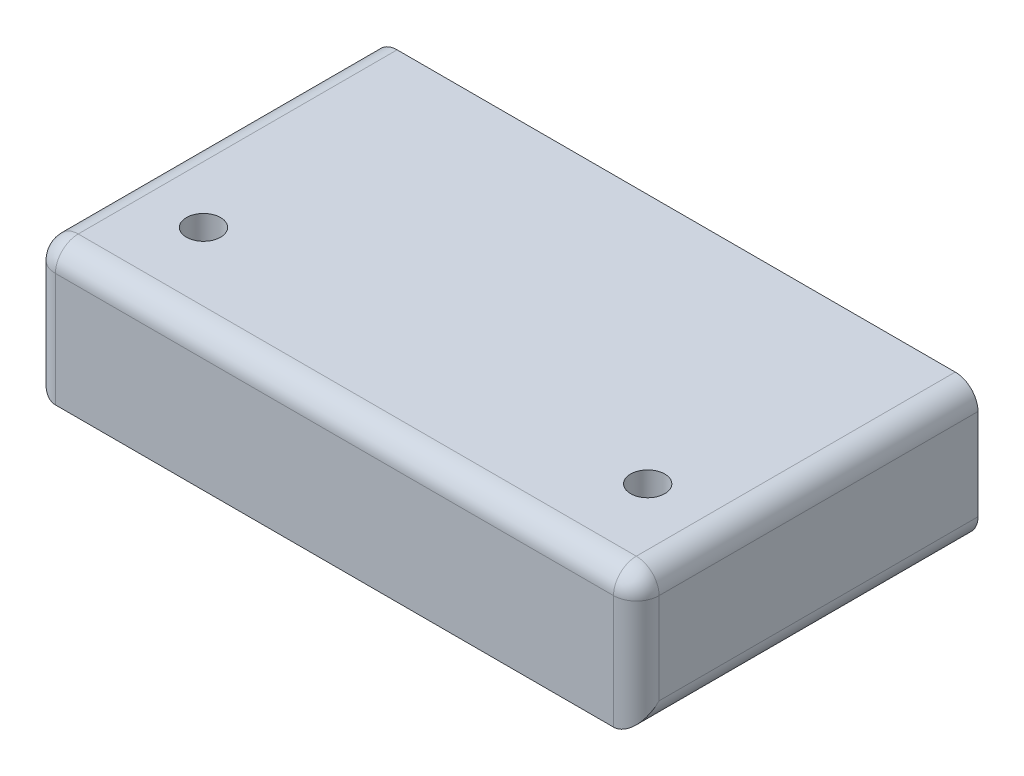
SolidWorks part; units mm, degrees
ref_plane "Front Plane" through (0, 0, 0) normal (0, 0, 1) x (1, 0, 0)
ref_plane "Top Plane" through (0, 0, 0) normal (0, 1, 0) x (1, 0, 0)
ref_plane "Right Plane" through (0, 0, 0) normal (1, 0, 0) x (0, 0, -1)
sketch "Sketch1" plane through (0, 0, 0) normal (0, 0, 1) x (1, 0, 0)
  line L1 (-26.5, 6) -> (26.5, 6)
  line L2 (-26.5, 6) -> (-26.5, -6)
  line L3 (-26.5, -6) -> (26.5, -6)
  line L4 (26.5, 6) -> (26.5, -6)
  line L5 (-26.5, 6) -> (26.5, -6) construction
  line L6 (-26.5, -6) -> (26.5, 6) construction
  point P0 (0, 0)
  dimension "D1" = 12
  dimension "D2" = 53
extrude "Boss-Extrude1" add sketch "Sketch1" along normal blind 30
sketch "Sketch2" plane through (0, -6, 0) normal (0, -1, 0) x (1, 0, 0)
  line L0 (0, 0) -> (0, 30) construction
  line L1 (-26.5, 0) -> (26.5, 0) construction
  line L2 (-26.5, 30) -> (26.5, 30) construction
  line L3 (-19.5, 22) -> (19.5, 22) construction
  circle A0 centre (-19.5, 22) radius 1.5
  circle A1 centre (19.5, 22) radius 1.5
  point P8 (0, 22)
  dimension "D1" = 3
  dimension "D2" = 39
  dimension "D3" = 8
extrude "Cut-Extrude1" cut sketch "Sketch2" against normal up to next
fillet "Fillet1" radius 2 7 edges at (26.5, 0, 30) (0, 6, 30) (-26.5, 0, 30) (-26.5, 6, 15) (26.5, 6, 15) (26.5, -6, 15) (-26.5, -6, 15)
